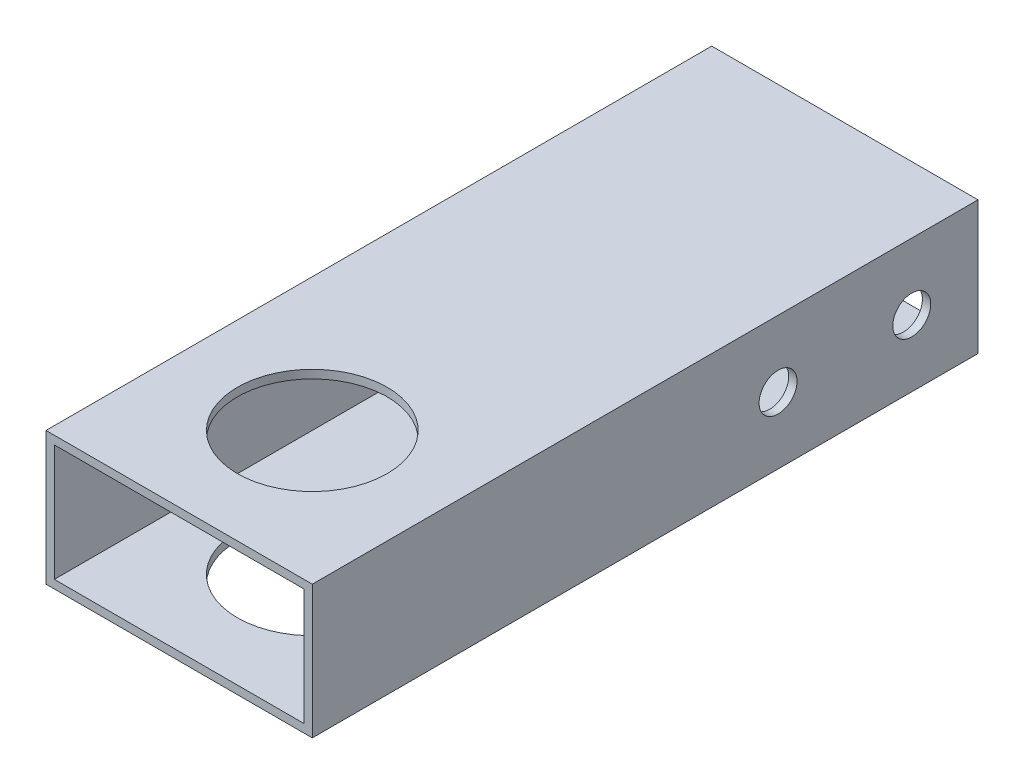
SolidWorks part; units mm, degrees
ref_plane "Front Plane" through (0, 0, 0) normal (0, 0, 1) x (1, 0, 0)
ref_plane "Top Plane" through (0, 0, 0) normal (0, 1, 0) x (1, 0, 0)
ref_plane "Right Plane" through (0, 0, 0) normal (1, 0, 0) x (0, 0, -1)
sketch "Sketch1" plane through (0, 0, 0) normal (0, 0, 1) x (1, 0, 0)
  line L1 (23.8125, -11.1125) -> (-23.8125, -11.1125)
  line L2 (23.8125, -11.1125) -> (23.8125, 11.1125)
  line L3 (23.8125, 11.1125) -> (-23.8125, 11.1125)
  line L4 (-23.8125, -11.1125) -> (-23.8125, 11.1125)
  line L5 (23.8125, -11.1125) -> (-23.8125, 11.1125) construction
  line L6 (23.8125, 11.1125) -> (-23.8125, -11.1125) construction
  line L7 (25.4, -12.7) -> (-25.4, -12.7)
  line L8 (25.4, -12.7) -> (25.4, 12.7)
  line L9 (25.4, 12.7) -> (-25.4, 12.7)
  line L10 (-25.4, -12.7) -> (-25.4, 12.7)
  line L11 (25.4, -12.7) -> (-25.4, 12.7) construction
  line L12 (25.4, 12.7) -> (-25.4, -12.7) construction
  point P0 (0, 0)
  point P6 (0, 0)
  dimension "D1" = 50.8
  dimension "D2" = 25.4
  dimension "D3" = 1.5875
  dimension "D4" = 1.5875
extrude "Boss-Extrude1" add sketch "Sketch1" along normal blind 127
sketch "Sketch2" plane through (0, -12.7, 0) normal (0, -1, 0) x (1, 0, 0)
  line L0 (0, 0) -> (0, 101.6) construction
  line L1 (-25.4, 0) -> (25.4, 0) construction
  circle A0 centre (0, 101.6) radius 14.2875
  dimension "D2" = 28.575
  dimension "D1" = 101.6
extrude "Cut-Extrude1" cut sketch "Sketch2" against normal through all
sketch "Sketch3" plane through (25.4, 0, 0) normal (1, 0, 0) x (0, 0, -1)
  line L0 (-34.5186, 0) -> (-16.256, 0)
  line L1 (-9.017, 0) -> (0, 0)
  line L2 (0, -12.7) -> (0, 12.7) construction
  line L3 (-12.6365, 0) -> (-12.6365, 12.7)
  line L4 (-127, 12.7) -> (0, 12.7) construction
  line L5 (0, 12.7) -> (0, 0)
  circle A0 centre (-38.1381, 0) radius 3.6195
  circle A3 centre (-12.6365, 0) radius 3.6195
  point P17 (0, 0)
  dimension "D1" = 7.239
  dimension "D2" = 18.2626
  dimension "D3" = 7.239
  dimension "D4" = 9.017
  dimension "D5" = 12.7
extrude "Cut-Extrude2" cut sketch "Sketch3" against normal through all and the other way through all contours A3 | A0 region at (25.4, 2.487, 15.1235) region at (25.4, 0, 38.1381)
